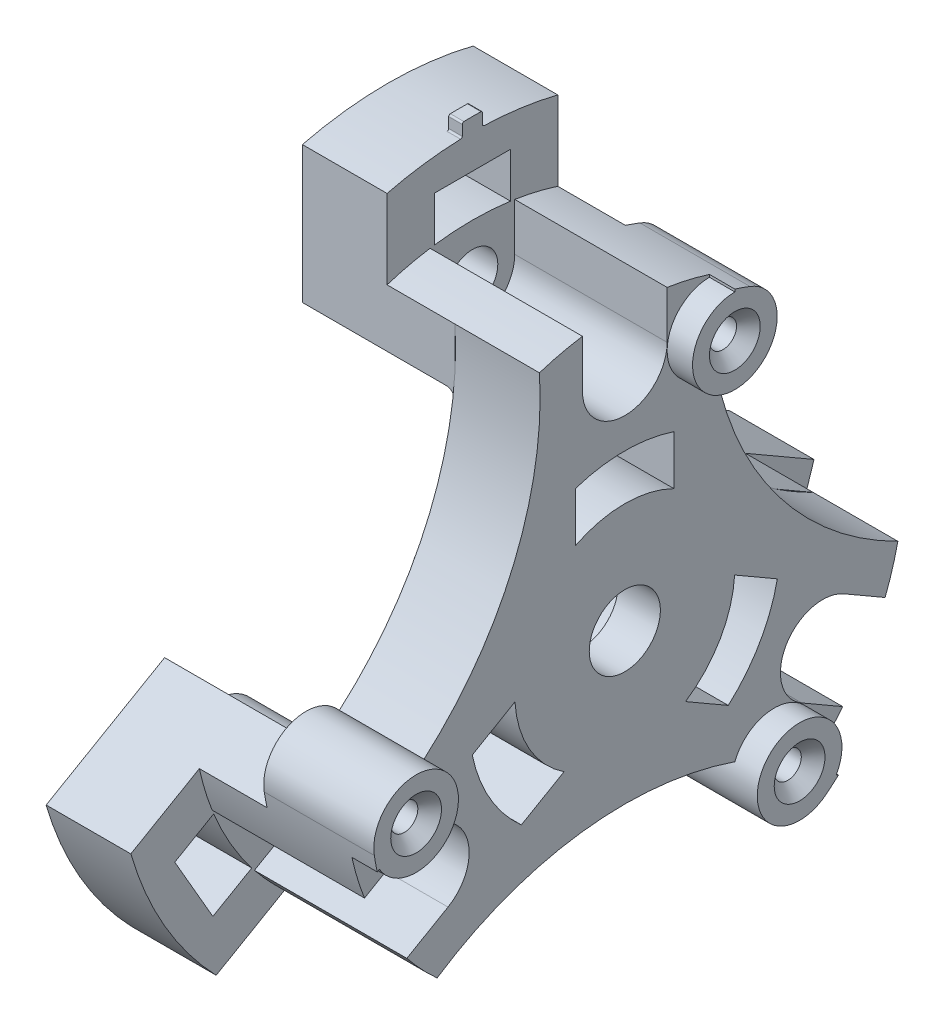
SolidWorks part; units mm, degrees
ref_plane "Front" through (0, 0, 0) normal (0, 0, 1) x (1, 0, 0)
ref_plane "Top" through (0, 0, 0) normal (0, 1, 0) x (1, 0, 0)
ref_plane "Right" through (0, 0, 0) normal (1, 0, 0) x (0, 0, -1)
sketch "草图1" plane through (0, 0, 0) normal (0, 0, 1) x (1, 0, 0)
  line L0 (-65.7429, 0) -> (89.5714, 0) construction
  line L1 (0, 67.1143) -> (0, -71.9143) construction
  line L2 (-7, 6.5) -> (-5, 6.5)
  line L3 (-5, 6.5) -> (-5, 16.5)
  line L4 (-5, 16.5) -> (0, 16.5)
  line L5 (0, 16.5) -> (0, 2.1)
  line L6 (-2.5, 4) -> (-7, 4)
  line L7 (-7, 4) -> (-7, 6.5)
  line L8 (-2.5, 4) -> (-2.5, 2.1)
  line L9 (-2.5, 2.1) -> (0, 2.1)
  dimension "D1" = 4.2
  dimension "D2" = 2.5
  dimension "D3" = 8
  dimension "D4" = 7
  dimension "D5" = 5
  dimension "D6" = 13
  dimension "D7" = 33
revolve "旋转1" add sketch "草图1" angle 360 about L0
sketch "草图2" plane through (-5, 0, 0) normal (-1, 0, 0) x (0, 0, 1)
  line L0 (-23.9515, 0) -> (26.381, 0) construction
  line L1 (0, 44.3891) -> (0, -20.5254) construction
  line L2 (0, 0) -> (-21.2641, -12.2768) construction
  line L3 (0, 0) -> (20.7932, -12.005) construction
  line L4 (0, 0) -> (-61.1055, 35.2793) construction
  line L5 (-5, 31.2128) -> (-5, 9) construction
  line L6 (5, 31.2128) -> (5, 9) construction
  circle A1 centre (-25, 14.4338) radius 20
  point P7 (0, 9)
  point P9 (-7.6795, 4.4338)
  dimension "D6" = 40
  dimension "D1" = 120
  dimension "D2" = 120
  dimension "D3" = 9
  dimension "D5" = 60
  dimension "D7" = 10
extrude "切除-拉伸1" cut sketch "草图2" against normal blind 10 contours A1
pattern_circular "阵列(圆周)1" count 3 over 360 about axis through (-7, 0, 0) along (-1, 0, 0) of "切除-拉伸1"
sketch "草图3" plane through (-5, 0, 0) normal (-1, 0, 0) x (0, 0, 1)
  line L0 (0, 18) -> (0, -12.9057) construction
  line L1 (-20.442, 0) -> (20.8303, 0) construction
  line L2 (-2.9, 8.731) -> (-2.9, 5.8172)
  line L4 (2.9, 8.731) -> (2.9, 5.8172)
  arc A0 (2.9, 8.731) -> (-2.9, 8.731) centre (0, 0) ccw
  circle A1 centre (0, 0) radius 6.5 construction
  arc A2 (2.9, 5.8172) -> (-2.9, 5.8172) centre (0, 0) ccw
  dimension "D1" = 9.2
  dimension "D2" = 5.8
extrude "切除-拉伸2" cut sketch "草图3" against normal blind 10
pattern_circular "阵列(圆周)2" count 3 over 360 about axis through (-2.5, 0, 0) along (-1, 0, 0) of "切除-拉伸2"
sketch "草图4" plane through (-5, 0, 0) normal (-1, 0, 0) x (0, 0, 1)
  line L0 (-16.7535, 0) -> (15.8993, 0) construction
  line L1 (0, 19.3876) -> (0, -16.6742) construction
  line L2 (-5.0408, 15.7111) -> (-5.0408, 12.3077)
  line L4 (5.0408, 12.3077) -> (5.0408, 15.7111)
  circle A0 centre (0, 0) radius 13.5 construction
  arc A1 (5.0408, 15.7111) -> (-5.0408, 15.7111) centre (0, 0) ccw construction
  arc A2 (5.0408, 15.7111) -> (-5.0408, 15.7111) centre (0, 0) ccw
  circle A3 centre (0, 13.5) radius 1.5
  arc A4 (-2.757, 13.0111) -> (2.757, 13.0111) centre (0, 13.5) ccw
  arc A5 (-2.757, 13.0111) -> (-5.0408, 12.3077) centre (0, 0) ccw
  arc A6 (5.0408, 12.3077) -> (2.757, 13.0111) centre (0, 0) ccw
  dimension "D1" = 27
  dimension "D2" = 3
  dimension "D4" = 5.6
  dimension "D5" = 26.6
extrude "凸台-拉伸1" add sketch "草图4" along normal blind 9
pattern_circular "阵列(圆周)3" count 3 over 360 about axis through (-65.7429, 0, 0) along (-1, 0, 0) of "凸台-拉伸1"
sketch "草图5" plane through (-14, 0, 0) normal (-1, 0, 0) x (0, 0, 1)
  line L0 (-16.1323, 0) -> (16.637, 0) construction
  line L1 (0, 17.8058) -> (0, -12.3621) construction
  line L2 (-3.05, 14) -> (3.05, 14)
  line L3 (-3.05, 14) -> (-3.05, 9.2908)
  line L4 (-3.05, 9.2908) -> (3.05, 9.2908)
  line L5 (3.05, 14) -> (3.05, 9.2908)
  point P10 (0, 9.2908)
  point P11 (0, 14)
  dimension "D1" = 14
  dimension "D2" = 6.1
extrude "切除-拉伸3" cut sketch "草图5" against normal blind 1.5 draft 1 contours L4 L5 L2 L3
sketch "草图10" plane through (-5, 0, 0) normal (-1, 0, 0) x (0, 0, 1)
  point P1 (0, 0)
  dimension "D1" = 12.8775
pattern_circular "阵列(圆周)4" count 3 over 360 about axis through (-65.7429, 0, 0) along (-1, 0, 0) of "切除-拉伸3" reverse direction yes
sketch "草图6" plane through (0, 0, 0) normal (1, 0, 0) x (0, 0, -1)
  line L0 (-17.245, 0) -> (20.4566, 0) construction
  line L1 (0, 20.1005) -> (0, -14.3306) construction
  line L2 (-2.5, 16.3095) -> (-2.5, 13.5)
  line L3 (2.5, 16.3095) -> (2.5, 13.5)
  circle A0 centre (0, 0) radius 13.5 construction
  arc A1 (5.0408, 15.7111) -> (-5.0408, 15.7111) centre (0, 0) ccw construction
  arc A3 (2.5, 16.3095) -> (-2.5, 16.3095) centre (0, 0) ccw
  arc A4 (-2.5, 13.5) -> (2.5, 13.5) centre (0, 13.5) ccw
  dimension "D1" = 27
  dimension "D3" = 5
  dimension "D2" = 5
extrude "切除-拉伸4" cut sketch "草图6" against normal blind 9
pattern_circular "阵列(圆周)5" count 3 over 360 about axis through (-65.7429, 0, 0) along (-1, 0, 0) of "切除-拉伸4"
sketch "草图7" plane through (-5, 0, 0) normal (-1, 0, 0) x (0, 0, 1)
  line L0 (0, 19.1221) -> (0, -13.8647) construction
  line L1 (16.0973, 0) -> (-17.961, 0) construction
  line L2 (-5, 15.5767) -> (-5, 15.7242)
  arc A1 (-5.8929, 15.4118) -> (-5, 15.5767) centre (-5, 13.0767) ccw
  circle A5 centre (0, 0) radius 14 construction
  arc A6 (-2.5, 16.3095) -> (-5.0408, 15.7111) centre (0, 0) ccw construction
  arc A7 (-5, 15.7242) -> (-5.8929, 15.4118) centre (0, 0) ccw
  point P7 (-5, 13.0767)
  dimension "D1" = 28
  dimension "D3" = 5
  dimension "D2" = 5
extrude "凸台-拉伸2" add sketch "草图7" against normal blind 6.5
sketch "草图9" plane through (1.5, 0, 0) normal (1, 0, 0) x (0, 0, -1)
  line L0 (0, 17.5729) -> (0, -10.6538) construction
  line L1 (-14.0745, 0) -> (16.4041, 0) construction
  circle A0 centre (0, 0) radius 14 construction
  circle A1 centre (5, 13.0767) radius 0.8
  dimension "D1" = 1.6
extrude "切除-拉伸7" cut sketch "草图9" against normal blind 6.4 contours A1
chamfer "倒角3" distance 0.7 angle 45 1 edges at (1.5, 13.0767, -5.8)
pattern_circular "阵列(圆周)8" count 3 over 360 about axis through (-65.7429, 0, 0) along (-1, 0, 0) of "凸台-拉伸2", "切除-拉伸7", "倒角3"
chamfer "倒角4" distance 0.3 angle 45 1 edges at (-7, 0, 4)
fillet "圆角5" radius 0.2 6 edges at (-13.2501, -9.1044, -9.6954) (-13.2501, -3.8443, -12.7323) (-13.2501, 12.9486, -3.0369) (-13.2501, 12.9486, 3.0369) (-13.2501, -3.8443, 12.7323) (-13.2501, -9.1044, 9.6954)
fillet "圆角6" radius 0.5 9 edges at (-5, 12.7108, 3.9147) (-5, 12.7108, -3.9147) (-5, 10.7, 0) (-5, -2.9651, -12.9653) (-5, -5.35, -9.2665) (-5, -9.7457, -9.0505) (-5, -9.7457, 9.0505) (-5, -2.9651, 12.9653) (-5, -5.35, 9.2665)
fillet "圆角7" radius 0.5 1 edges at (-7, 0, 6.5)
sketch "草图11" plane through (-14, 0, 0) normal (-1, 0, 0) x (0, 0, 1)
  line L0 (-24.0343, 0) -> (27.0991, 0) construction
  line L1 (0, 23.8854) -> (0, -19.7008) construction
  line L2 (-5.0408, 15.7111) -> (-5.0408, 20.386)
  line L3 (5.0408, 15.7111) -> (5.0408, 20.386)
  line L4 (-2.25, 19) -> (2.25, 19)
  line L5 (-2.25, 19) -> (-2.25, 16.3459)
  line L7 (2.25, 19) -> (2.25, 16.3459)
  arc A0 (5.0408, 20.386) -> (0, 21) centre (0, 0) ccw
  arc A1 (5.0408, 15.7111) -> (-5.0408, 15.7111) centre (0, 0) ccw construction
  arc A2 (5.0408, 15.7111) -> (2.25, 16.3459) centre (0, 0) ccw
  arc A3 (-2.25, 16.3459) -> (-5.0408, 15.7111) centre (0, 0) ccw
  arc A4 (0, 21) -> (-5.0408, 20.386) centre (0, 0) ccw
  point P15 (0, 17)
  point P16 (0, 19)
  point P20 (0, 22)
  dimension "D1" = 42
  dimension "D2" = 4.5
  dimension "D3" = 19
extrude "凸台-拉伸3" add sketch "草图11" against normal up to surface (5 mm away) up to face at (-9, 13.5, -1.5)
pattern_circular "阵列(圆周)9" count 3 over 360 about axis through (-6.7, 0, 0) along (-1, 0, 0) of "凸台-拉伸3"
sketch "草图12" plane through (-9, 0, 0) normal (1, 0, 0) x (0, 0, -1)
  line L0 (0, 23.0537) -> (0, -15.9342) construction
  line L1 (-23.5138, 0) -> (22.1093, 0) construction
  line L2 (-0.6, 21.7917) -> (-0.6, 20.9914)
  line L3 (0.6, 21.7917) -> (0.6, 20.9914)
  arc A0 (0.6, 21.7917) -> (-0.6, 21.7917) centre (0, 0) ccw
  arc A1 (5.0408, 20.386) -> (-5.0408, 20.386) centre (0, 0) ccw construction
  arc A2 (0.6, 20.9914) -> (-0.6, 20.9914) centre (0, 0) ccw
  arc A3 (-21.8, 0) -> (21.8, 0) centre (0, 0) ccw
  dimension "D2" = 0.8
  dimension "D1" = 1.2
extrude "凸台-拉伸4" add sketch "草图12" against normal blind 0.8 contours A0 L2 A2 L3
fillet "圆角8" radius 0.1 4 edges at (-9.4, 20.9914, -0.6) (-9.4, 20.9914, 0.6) (-9.4, 21.7917, -0.6) (-9.4, 21.7917, 0.6)
